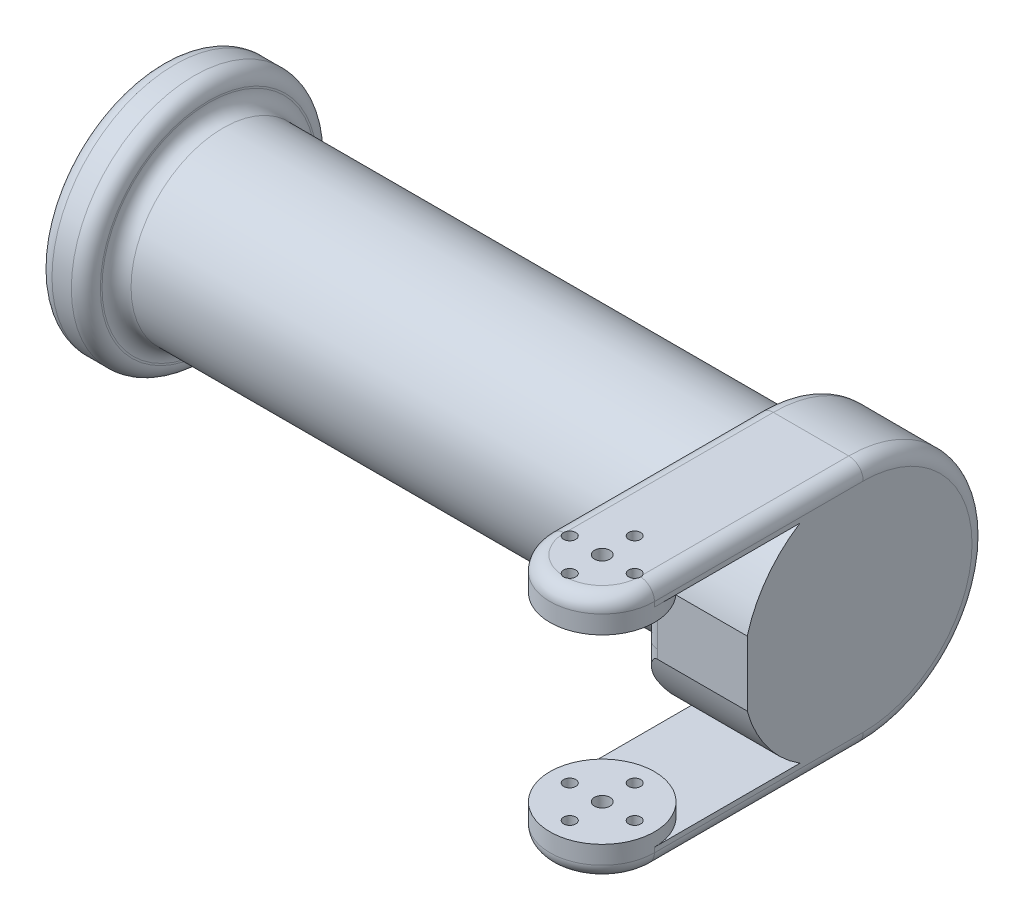
SolidWorks part; units mm, degrees
ref_plane "Front Plane" through (0, 0, 0) normal (0, 0, 1) x (1, 0, 0)
ref_plane "Top Plane" through (0, 0, 0) normal (0, 1, 0) x (1, 0, 0)
ref_plane "Right Plane" through (0, 0, 0) normal (1, 0, 0) x (0, 0, -1)
sketch "Sketch1" plane through (0, 0, 0) normal (1, 0, 0) x (0, 0, -1)
  line L0 (0, 10.97) -> (80, 10.97)
  line L1 (80, 10.97) -> (80, -10.97)
  line L2 (0, -10.97) -> (80, -10.97)
  arc A0 (0, 10.97) -> (0, -10.97) centre (0, 0) ccw
  dimension "D1" = 21.94
  dimension "D2" = 80
extrude "Boss-Extrude1" add sketch "Sketch1" along normal blind 15
sketch "Sketch2" plane through (15, 0, 0) normal (1, 0, 0) x (0, 0, -1)
  line L0 (0, 28.05) -> (0, -28.05) construction
  circle A0 centre (0, 0) radius 10.97
  circle A1 centre (0, 0) radius 1.6
  circle A2 centre (0, 6.58) radius 1.25
  circle A3 centre (6.58, 0) radius 1.25
  circle A4 centre (0, -6.58) radius 1.25
  circle A5 centre (-6.58, 0) radius 1.25
  point P17 (0, 0)
  dimension "D1" = 3.2
  dimension "D2" = 2.5
  dimension "D3" = 6.58
  dimension "D4" = 4
extrude "Boss-Extrude2" add sketch "Sketch2" along normal blind 5.89
sketch "Sketch3" plane through (20.89, 0, 0) normal (1, 0, 0) x (0, 0, -1)
  circle A0 centre (0, 6.58) radius 1.25
  circle A1 centre (0, 0) radius 1.6
  circle A2 centre (0, -6.58) radius 1.25
  circle A3 centre (-6.58, 0) radius 1.25
  circle A4 centre (6.58, 0) radius 1.25
extrude "Cut-Extrude1" cut sketch "Sketch3" against normal blind 100
sketch "Sketch4" plane through (15, 0, 0) normal (1, 0, 0) x (0, 0, -1)
  line L0 (80, 10.97) -> (0, 10.97) construction
  line L1 (30, 10.97) -> (80, 10.97)
  line L2 (30, 10.97) -> (30, -10.97)
  line L3 (30, -10.97) -> (80, -10.97)
  line L4 (80, 10.97) -> (80, -10.97)
  dimension "D1" = 30
extrude "Boss-Extrude3" add sketch "Sketch4" along normal blind 49.02
sketch "Sketch5" plane through (0, 0, 0) normal (0, 1, 0) x (1, 0, 0)
  line L0 (0, -12.067) -> (0, 12.067) construction
  line L1 (64.02, 34.7595) -> (0, 34.7595) construction
  line L2 (64.02, 80) -> (64.02, 30) construction
  line L3 (32.01, 80) -> (32.01, -10.8477) construction
  line L4 (64.02, 80) -> (0, 80) construction
sketch "Sketch6" plane through (0, 10.97, 0) normal (0, 1, 0) x (1, 0, 0)
  line L0 (64.02, 80) -> (0, 80) construction
  line L1 (15, 30) -> (44, 30)
  line L2 (15, 30) -> (15, 80)
  line L3 (15, 80) -> (44, 80)
  line L4 (44, 30) -> (44, 80)
sketch "Sketch9" plane through (0, 0, 0) normal (-1, 0, 0) x (0, 0, 1)
  line L0 (-80, 0) -> (10.8477, 0) construction
  line L1 (-80, 25.5) -> (-29, 25.5)
  line L2 (-80, 25.5) -> (-80, -25.5)
  line L3 (-80, -25.5) -> (-29, -25.5)
  line L4 (-29, 25.5) -> (-29, -25.5)
  line L5 (-80, 25.5) -> (-29, -25.5) construction
  line L6 (-80, -25.5) -> (-29, 25.5) construction
  line L7 (-80, 10.97) -> (-80, -10.97) construction
  point P0 (-54.5, 0)
  dimension "D1" = 29
  dimension "D2" = 25.5
  dimension "D3" = 0
extrude "Boss-Extrude7" add sketch "Sketch9" along normal blind 10
sketch "Sketch10" plane through (-10, 0, 0) normal (-1, 0, 0) x (0, 0, 1)
  line L0 (-80, 0) -> (-29, 0) construction
  line L1 (-80, 10.97) -> (-80, -10.97) construction
  line L2 (-29, -25.5) -> (-29, 25.5) construction
  circle A0 centre (-54.5, 0) radius 19.05
  dimension "D1" = 38.1
extrude "Boss-Extrude8" add sketch "Sketch10" along normal blind 114.3
sketch "Sketch11" plane through (-124.3, 0, 0) normal (-1, 0, 0) x (0, 0, 1)
  line L0 (-73.55, 0) -> (-35.45, 0) construction
  line L1 (-80, 0) -> (10.8477, 0) construction
  circle A0 centre (-54.5, 0) radius 19.05 construction
  circle A1 centre (-54.5, 0) radius 25.4
  dimension "D1" = 50.8
extrude "Boss-Extrude9" add sketch "Sketch11" along normal blind 10
sketch "Sketch12" plane through (0, 0, -30) normal (0, 0, 1) x (1, 0, 0)
  line L0 (64.02, -10.97) -> (15, -10.97) construction
  line L1 (64.02, 10.97) -> (49.02, 10.97)
  line L2 (64.02, 10.97) -> (64.02, -10.97)
  line L3 (64.02, -10.97) -> (49.02, -10.97)
  line L4 (49.02, 10.97) -> (49.02, -10.97)
  dimension "D1" = 15
extrude "Boss-Extrude10" add sketch "Sketch12" along normal blind 30
sketch "Sketch13" plane through (64.02, 0, 0) normal (1, 0, 0) x (0, 0, -1)
  circle A0 centre (0, 0) radius 10.97
  circle A1 centre (0, 0) radius 1.6
  circle A2 centre (6.58, 0) radius 1.25
  circle A3 centre (0, 6.58) radius 1.25
  circle A4 centre (0, -6.58) radius 1.25
  circle A5 centre (-6.58, 0) radius 1.25
  point P17 (0, 0)
  dimension "D1" = 4
extrude "Boss-Extrude11" add sketch "Sketch13" against normal blind 20.89
sketch "Sketch15" plane through (64.02, 0, 0) normal (1, 0, 0) x (0, 0, -1)
  circle A0 centre (0, 0) radius 1.6
  circle A1 centre (0, 6.58) radius 1.25
  circle A2 centre (6.58, 0) radius 1.25
  circle A3 centre (0, -6.58) radius 1.25
  circle A4 centre (-6.58, 0) radius 1.25
  point P15 (0, 0)
  dimension "D1" = 4
extrude "Cut-Extrude2" cut sketch "Sketch15" against normal blind 20.89
sketch "Sketch17" plane through (0, 0, 0) normal (1, 0, 0) x (0, 0, -1)
  line L1 (29, 25.5) -> (80, 25.5)
  line L2 (29, 25.5) -> (29, -25.5)
  line L3 (29, -25.5) -> (80, -25.5)
  line L4 (80, 25.5) -> (80, -25.5)
extrude "Boss-Extrude12" add sketch "Sketch17" along normal blind 79.02
sketch "Sketch18" plane through (0, 0, -29) normal (0, 0, 1) x (1, 0, 0)
  line L1 (39.5513, 13.4042) -> (70.044, 13.4042)
  line L2 (39.5513, 13.4042) -> (39.5513, -17.0884)
  line L3 (39.5513, -17.0884) -> (70.044, -17.0884)
  line L4 (70.044, 13.4042) -> (70.044, -17.0884)
extrude "Cut-Extrude3" cut sketch "Sketch18" along normal blind 64
sketch "Sketch19" plane through (0, 0, -29) normal (0, 0, 1) x (1, 0, 0)
  line L0 (79.02, 25.5) -> (79.02, -25.5) construction
  line L1 (79.02, 10.97) -> (64.02, 10.97)
  line L2 (79.02, 10.97) -> (79.02, -10.97)
  line L3 (79.02, -10.97) -> (64.02, -10.97)
  line L4 (64.02, 10.97) -> (64.02, -10.97)
  line L5 (50.0335, 0) -> (-50.0335, 0) construction
  dimension "D1" = 15
  dimension "D2" = 21.94
  dimension "D3" = 10.97
extrude "Boss-Extrude13" add sketch "Sketch19" along normal blind 29
sketch "Sketch20" plane through (79.02, 0, 0) normal (1, 0, 0) x (0, 0, -1)
  circle A0 centre (0, 0) radius 10.97
  circle A1 centre (0, 0) radius 1.6
  circle A2 centre (0, 6.58) radius 1.25
  circle A3 centre (6.58, 0) radius 1.25
  circle A4 centre (0, -6.58) radius 1.25
  circle A5 centre (-6.58, 0) radius 1.25
  point P17 (0, 0)
  dimension "D1" = 4
extrude "Boss-Extrude14" add sketch "Sketch20" against normal blind 20.98
sketch "Sketch21" plane through (79.02, 0, 0) normal (1, 0, 0) x (0, 0, -1)
  circle A0 centre (0, 0) radius 1.6
  circle A1 centre (0, 6.58) radius 1.25
  circle A2 centre (6.58, 0) radius 1.25
  circle A3 centre (0, -6.58) radius 1.25
  circle A4 centre (-6.58, 0) radius 1.25
  point P14 (0, 0)
  dimension "D1" = 4
extrude "Cut-Extrude4" cut sketch "Sketch21" against normal blind 20.98
sketch "Sketch23" plane through (79.02, 0, 0) normal (1, 0, 0) x (0, 0, -1)
  line L0 (29, -10.97) -> (29, -25.5) construction
  line L1 (-13.4821, 15.5896) -> (29, 15.5896)
  line L2 (-13.4821, 15.5896) -> (-13.4821, -18.235)
  line L3 (-13.4821, -18.235) -> (29, -18.235)
  line L4 (29, 15.5896) -> (29, -18.235)
extrude "Cut-Extrude6" cut sketch "Sketch23" against normal blind 100
sketch "Sketch27" plane through (0, 0, -29) normal (0, 0, 1) x (1, 0, 0)
  line L1 (50.0335, 0) -> (-50.0335, 0) construction
  line L2 (25.67, 18.75) -> (52.37, 18.75)
  line L3 (25.67, 18.75) -> (25.67, -18.75)
  line L4 (25.67, -18.75) -> (52.37, -18.75)
  line L5 (52.37, 18.75) -> (52.37, -18.75)
  line L6 (25.67, 18.75) -> (52.37, -18.75) construction
  line L7 (25.67, -18.75) -> (52.37, 18.75) construction
  line L8 (79.02, 25.5) -> (79.02, -25.5) construction
  point P2 (39.02, 0)
  dimension "D1" = 26.7
  dimension "D2" = 37.5
  dimension "D3" = 40
sketch "Sketch24" plane through (0, 25.5, 0) normal (0, 1, 0) x (1, 0, 0)
  line L0 (-10, 54.5) -> (79.02, 54.5) construction
  line L1 (-10, 29) -> (-10, 80) construction
  line L2 (79.02, 80) -> (79.02, 29) construction
  circle A0 centre (34.51, 54.5) radius 1.6
  circle A1 centre (34.51, 61.08) radius 1.25
  circle A2 centre (41.09, 54.5) radius 1.25
  circle A3 centre (34.51, 47.92) radius 1.25
  circle A4 centre (27.93, 54.5) radius 1.25
  dimension "D1" = 3.2
  dimension "D2" = 2.5
  dimension "D3" = 6.58
  dimension "D4" = 4
sketch "Sketch31" plane through (0, 25.5, 0) normal (0, 1, 0) x (1, 0, 0)
  line L0 (-28.05, 0) -> (28.05, 0) construction
  line L1 (-10, 80) -> (40.8, 80)
  line L2 (-10, 80) -> (-10, 0)
  line L3 (-10, 0) -> (40.8, 0)
  line L4 (40.8, 80) -> (40.8, 0)
  dimension "D1" = 50.8
extrude "Boss-Extrude15" add sketch "Sketch31" against normal blind 51
sketch "Sketch32" plane through (0, 25.5, 0) normal (0, 1, 0) x (1, 0, 0)
  line L0 (-10, 80) -> (79.02, 80) construction
  line L1 (79.02, 29) -> (40.8, 29)
  line L2 (79.02, 29) -> (79.02, 80)
  line L3 (79.02, 80) -> (40.8, 80)
  line L4 (40.8, 29) -> (40.8, 80)
extrude "Cut-Extrude9" cut sketch "Sketch32" against normal blind 51
sketch "Sketch33" plane through (0, 25.5, 0) normal (0, 1, 0) x (1, 0, 0)
  line L0 (-28.05, 0) -> (28.05, 0) construction
  line L1 (-10, 0) -> (-10, 80) construction
  line L2 (-10, 10.8) -> (-10, 0)
  line L3 (-10, 0) -> (0.8, 0)
  line L4 (0.8, 0) -> (11.6, 0)
  line L5 (11.6, 0) -> (11.6, 10.8)
  line L6 (11.6, 10.8) -> (11.6, 80)
  line L7 (-10, 80) -> (40.8, 80) construction
  line L8 (11.6, 80) -> (-10, 80)
  line L9 (-10, 80) -> (-9.9604, 11.7241)
  line L10 (40.8, 0) -> (40.8, 80) construction
  line L11 (11.6, 80) -> (40.8, 80)
  line L12 (11.6, 80) -> (11.6, 0)
  line L13 (11.6, 0) -> (40.8, 0)
  line L14 (40.8, 80) -> (40.8, 0)
  circle A0 centre (0.8, 10.8) radius 10.8
  circle A1 centre (0.8, 10.8) radius 1.6
  circle A2 centre (0.8, 17.5188) radius 1.25
  circle A3 centre (7.5188, 10.8) radius 1.25
  circle A4 centre (0.8, 4.0812) radius 1.25
  circle A5 centre (-5.9188, 10.8) radius 1.25
  line M4 (40.8, 0) -> (40.8, 80)
  line M5 (40.8, 80) -> (-10, 80)
  line M6 (-10, 80) -> (-10, 0)
  line M7 (-10, 0) -> (40.8, 0)
  dimension "D1" = 21.6
  dimension "D4" = 3.2
  dimension "D5" = 2.5
  dimension "D2" = 10.8
  dimension "D3" = 10.8
  dimension "D6" = 4
extrude "Cut-Extrude10" cut sketch "Sketch33" against normal blind 51 contours A0 M6 M7 | A0 L5 M7 | L6 L5 M7 M4 M5 | A2 | A5 | A3 | A4 | A1 region at (-7.5876, 25.5, -2.4124) region at (9.1876, 25.5, -2.4124) region at (26.2, 25.5, -40) region at (0.8, 25.5, -10.8) region at (0.8, 25.5, -17.5188) region at (7.5188, 25.5, -10.8) region at (0.8, 25.5, -4.0812) region at (-5.9188, 25.5, -10.8)
sketch "Sketch35" plane through (11.6, 0, 0) normal (1, 0, 0) x (0, 0, -1)
  line L0 (0, 28.05) -> (0, -28.05) construction
  line L1 (0, 21.5) -> (30, 21.5)
  line L2 (0, 21.5) -> (0, -21.5)
  line L3 (0, -21.5) -> (30, -21.5)
  line L4 (30, 21.5) -> (30, -21.5)
  line L5 (44, 0) -> (-44, 0) construction
  dimension "D1" = 43
  dimension "D2" = 21.5
  dimension "D3" = 30
extrude "Cut-Extrude11" cut sketch "Sketch35" against normal blind 51
sketch "Sketch36" plane through (0, -25.5, 0) normal (0, -1, 0) x (1, 0, 0)
  circle A0 centre (0.8, -10.8) radius 10.8
  circle A1 centre (0.8, -10.8) radius 1.6
  circle A2 centre (0.8, -4.0812) radius 1.25
  circle A3 centre (7.5188, -10.8) radius 1.25
  circle A4 centre (0.8, -17.5188) radius 1.25
  circle A5 centre (-5.9188, -10.8) radius 1.25
  dimension "D1" = 4
extrude "Boss-Extrude16" add sketch "Sketch36" against normal blind 6.75
sketch "Sketch37" plane through (0, 25.5, 0) normal (0, 1, 0) x (1, 0, 0)
  circle A0 centre (0.8, 10.8) radius 10.8
  circle A1 centre (0.8, 10.8) radius 1.6
  circle A2 centre (0.8, 17.5188) radius 1.25
  circle A3 centre (7.5188, 10.8) radius 1.25
  circle A4 centre (0.8, 4.0812) radius 1.25
  circle A5 centre (-5.9188, 10.8) radius 1.25
  dimension "D1" = 4
extrude "Boss-Extrude17" add sketch "Sketch37" against normal blind 6.75
sketch "Sketch38" plane through (-10, 0, 0) normal (-1, 0, 0) x (0, 0, 1)
  line L0 (-80, -25.5) -> (-10.8, -25.5) construction
  line L5 (-80, 25.5) -> (-53.9876, 25.5)
  line L6 (-80, 25.5) -> (-80, -25.5)
  line L7 (-80, -25.5) -> (-53.9876, -25.5)
  line L8 (-53.9876, 25.5) -> (-53.9876, -25.5)
  circle A2 centre (-53.9876, 0) radius 25.5
  line M7 (-10.8, 25.5) -> (-80, 25.5)
  line M8 (-80, 25.5) -> (-80, -25.5)
extrude "Cut-Extrude12" cut sketch "Sketch38" against normal blind 100 contours L7 M7 M8 region at (-10, 24.9275, -66.9938)
fillet "Fillet6" radius 3 3 edges at (-10, 0, -35.45) (-124.3, 0, -29.1) (-124.3, 0, -35.45)
fillet "Fillet7" radius 3 1 edges at (-134.3, 0, -29.1)
fillet "Fillet12" radius 3 9 edges at (-10, 0, -79.4876) (0.8, 25.5, 0) (0.8, -25.5, 0) (11.6, -25.5, -32.3938) (11.6, 25.5, -32.3938) (11.6, 0, -79.4876) (-10, 25.5, -32.3938) (-10, -25.5, -32.3938) (-10, 0, -30)
sketch "Sketch39" plane through (-10, 0, 0) normal (-1, 0, 0) x (0, 0, 1)
  line L0 (-30, -6.716) -> (-30, -21.5)
  line L1 (-30, 21.5) -> (-40.8825, 21.5)
  line L2 (-30, 21.5) -> (-30, 6.7158)
  line L3 (-30, -21.5) -> (-40.8821, -21.5)
  arc A0 (-40.8821, -21.5) -> (-30, -6.716) centre (-54.6074, -0.0001) ccw
  arc A1 (-30, 6.7158) -> (-40.8825, 21.5) centre (-54.6074, -0.0001) ccw
extrude "Cut-Extrude14" cut sketch "Sketch39" against normal blind 100
